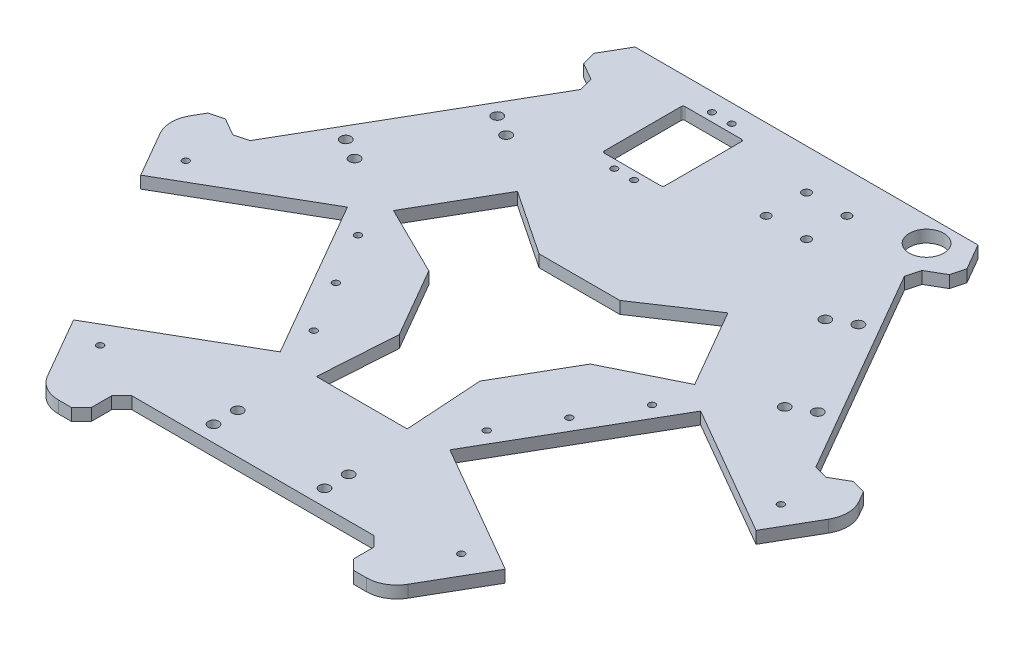
SolidWorks part; units mm, degrees
material "5052-O"
ref_plane "前基準面" through (0, 0, 0) normal (0, 0, 1) x (1, 0, 0)
ref_plane "上基準面" through (0, 0, 0) normal (0, 1, 0) x (1, 0, 0)
ref_plane "右基準面" through (0, 0, 0) normal (1, 0, 0) x (0, 0, -1)
sketch "草圖1" plane through (0, 0, 0) normal (0, 1, 0) x (1, 0, 0)
  line L1 (85, 147.2243) -> (-85, 147.2243)
  line L2 (-85, 147.2243) -> (-170, 0)
  line L3 (-170, 0) -> (-85, -147.2243)
  line L4 (-85, -147.2243) -> (85, -147.2243)
  line L5 (85, -147.2243) -> (170, 0)
  line L6 (170, 0) -> (85, 147.2243)
  circle A0 centre (0, 0) radius 147.2243 construction
  dimension "D1" = 170
extrude "填料-伸長1" add sketch "草圖1" along normal blind 6
ref_axis "基準軸1" through (0, -0.25, 0) along (0, 1, 0)
sketch "草圖46" plane through (0, 6, 0) normal (0, 1, 0) x (1, 0, 0)
  line L0 (-65, -147.2243) -> (65, -147.2243)
  line L1 (-65, -147.2243) -> (-65, -127.2243)
  line L2 (65, -147.2243) -> (65, -127.2243)
  line L3 (-65, -127.2243) -> (65, -127.2243)
  line L4 (-85, -147.2243) -> (85, -147.2243) construction
  point P6 (0, -147.2243)
  point P7 (0, -147.2243)
  dimension "D1" = 20
  dimension "D2" = 130
extrude "除料-伸長31" cut sketch "草圖46" against normal up to next
sketch "草圖8" plane through (0, 6, 0) normal (0, 1, 0) x (1, 0, 0)
  line L0 (65, -127.2243) -> (-65, -127.2243) construction
  line L2 (-27.5, -107.2243) -> (27.5, -107.2243) construction
  line L3 (-27.5, -107.2243) -> (-27.5, -119.2243) construction
  line L4 (-27.5, -119.2243) -> (27.5, -119.2243) construction
  line L5 (27.5, -107.2243) -> (27.5, -119.2243) construction
  circle A0 centre (-27.5, -119.2243) radius 2.6
  circle A1 centre (27.5, -119.2243) radius 2.6
  circle A2 centre (-27.5, -107.2243) radius 2.6
  circle A3 centre (27.5, -107.2243) radius 2.6
  point P7 (0, -119.2243)
  point P14 (0, -127.2243)
  dimension "D3" = 5.2
  dimension "D1" = 55
  dimension "D2" = 12
  dimension "D4" = 8
extrude "除料-伸長6" cut sketch "草圖8" against normal through all
pattern_circular "環狀複製排列1" count 3 over 360 about axis through (0, -0.25, 0) along (0, 1, 0) of "除料-伸長6", "除料-伸長31"
chamfer "導角1" distance 5 angle 45 12 edges at (65, 3, 127.2243) (65, 3, 147.2243) (-65, 3, 147.2243) (-65, 3, 127.2243) (77.6795, 3, -119.9038) (95, 3, -129.9038) (160, 3, -17.3205) (142.6795, 3, -7.3205) (-160, 3, -17.3205) (-142.6795, 3, -7.3205) (-77.6795, 3, -119.9038) (-95, 3, -129.9038)
sketch "草圖5" plane through (0, 6, 0) normal (0, 1, 0) x (1, 0, 0)
  line L0 (-152.5, -30.3109) -> (-107, -109.1192)
  line L1 (-152.5, -30.3109) -> (-87.5481, 7.1891)
  line L2 (-107, -109.1192) -> (-42.0481, -71.6192)
  line L3 (-87.5481, 7.1891) -> (-42.0481, -71.6192)
  line L4 (-170, 0) -> (-85, -147.2243) construction
  dimension "D1" = 75
  dimension "D2" = 91
  dimension "35" = 35
extrude "除料-伸長4" cut sketch "草圖5" against normal through all
sketch "草圖9" plane through (0, 6, 0) normal (0, 1, 0) x (1, 0, 0)
  line L0 (-64.7981, -32.215) -> (-118.4917, -63.215) construction
  line L1 (-42.0481, -71.6192) -> (-87.5481, 7.1891) construction
  line L2 (-118.4917, -63.215) -> (-89.4917, -113.4445) construction
  line L3 (-118.4917, -63.215) -> (-147.4917, -12.9856) construction
  circle A0 centre (-89.4917, -113.4445) radius 1.65
  circle A1 centre (-147.4917, -12.9856) radius 1.65
  dimension "D2" = 3.3
  dimension "D1" = 58
  dimension "D3" = 62
  dimension "D4" = 58
extrude "除料-伸長7" cut sketch "草圖9" against normal through all
mirror "鏡射1" about plane through (0, 0, 0) normal (1, 0, 0) of "除料-伸長4", "除料-伸長7"
fillet "圓角1" radius 15 4 edges at (170, 3, 0) (85, 3, 147.2243) (-170, 3, 0) (-85, 3, 147.2243)
sketch "草圖36" plane through (0, 6, 0) normal (0, 1, 0) x (1, 0, 0)
  line L0 (-72.8699, -2.2343) -> (-57.8699, -28.215) construction
  line L1 (-42.0481, -71.6192) -> (-87.5481, 7.1891) construction
  line L2 (-42.8699, -54.1958) -> (-57.8699, -28.215) construction
  line L3 (-57.8699, -28.215) -> (-64.7981, -32.215) construction
  circle A0 centre (-57.8699, -28.215) radius 1.25
  circle A1 centre (-42.8699, -54.1958) radius 1.25
  circle A2 centre (-72.8699, -2.2343) radius 1.25
  point P7 (-50.3699, -41.2054)
  point P10 (-64.7981, -32.215)
  dimension "D3" = 2.5
  dimension "D1" = 30
  dimension "D2" = 30
  dimension "D4" = 8
hole_wizard "M4x0.7 螺紋孔4" positions "草圖40" profile "草圖41" tap size "M4x0.7" standard "Ansi Metric" end condition through all
sketch "草圖40" plane through (0, 6, 0) normal (0, 1, 0) x (1, 0, 0)
  point P0 (-72.8699, -2.2343)
  point P3 (-57.8699, -28.215)
  point P6 (-42.8699, -54.1958)
sketch "草圖41" plane through (-72.8699, 6, 2.2343) normal (1, 0, 0) x (0, 0, 1)
  line L0 (0, 0) -> (0, 6)
  line L1 (0, 6) -> (1.65, 6)
  line L2 (1.65, 6) -> (1.65, 0)
  line L5 (1.65, 0) -> (0, 0)
  line L11 (0, -6.35) -> (0, 107.95) construction
  dimension "貫穿螺孔鑽直徑" = 3.3
  dimension "貫穿螺孔鑽深度" = 6
cosmetic thread "鑽孔螺紋1" parameters "D1"=10, "D2"=4.3
cosmetic thread "鑽孔螺紋2" parameters "D1"=10, "D2"=4.3
cosmetic thread "鑽孔螺紋3" parameters "D1"=10, "D2"=4.3
mirror "鏡射2" about plane through (0, 0, 0) normal (1, 0, 0) of "M4x0.7 螺紋孔4"
sketch "草圖51" plane through (0, 6, 0) normal (0, 1, 0) x (1, 0, 0)
  line L0 (85, 147.2243) -> (-85, 147.2243) construction
  line L1 (20, 34.641) -> (-20, 34.641)
  line L2 (-20, 34.641) -> (-40, 0)
  line L3 (-40, 0) -> (-20, -34.641)
  line L4 (-20, -34.641) -> (20, -34.641)
  line L5 (20, -34.641) -> (40, 0)
  line L6 (40, 0) -> (20, 34.641)
  circle A0 centre (0, 0) radius 34.641 construction
  dimension "D1" = 40
extrude "除料-伸長35" cut sketch "草圖51" against normal up to next
sketch "草圖52" plane through (0, 6, 0) normal (0, 1, 0) x (1, 0, 0)
  line L0 (-22.5, -73.2243) -> (22.5, -73.2243)
  line L5 (22.5, -73.2243) -> (20, -34.641)
  line L6 (20, -34.641) -> (-20, -34.641)
  line L7 (-20, -34.641) -> (-22.5, -73.2243)
  line L8 (60, -127.2243) -> (-60, -127.2243) construction
  line L9 (-20, 34.641) -> (-52.1641, 56.0977)
  line L10 (-52.1641, 56.0977) -> (-74.6641, 17.1266)
  line L11 (-74.6641, 17.1266) -> (-40, 0)
  line L12 (-40, 0) -> (-20, 34.641)
  line L13 (40, 0) -> (74.6641, 17.1266)
  line L14 (74.6641, 17.1266) -> (52.1641, 56.0977)
  line L15 (52.1641, 56.0977) -> (20, 34.641)
  line L16 (20, 34.641) -> (40, 0)
  line L17 (0, 0) -> (-20, -34.641) construction
  line L18 (0, 0) -> (-20, 34.641) construction
  point P8 (0, -73.2243)
  point P9 (0, -127.2243)
  dimension "D1" = 54
  dimension "D2" = 45
  dimension "D4" = 120
  dimension "D3" = 3
extrude "除料-伸長36" cut sketch "草圖52" against normal up to next
sketch "草圖53" plane through (0, 6, 0) normal (0, 1, 0) x (1, 0, 0)
  line L0 (85, 147.2243) -> (-85, 147.2243) construction
  line L1 (20, 127.2243) -> (40, 127.2243) construction
  line L2 (20, 127.2243) -> (20, 107.2243) construction
  line L3 (20, 107.2243) -> (40, 107.2243) construction
  line L4 (40, 127.2243) -> (40, 107.2243) construction
  line L5 (20, 127.2243) -> (-85, 127.2243) construction
  line L6 (-85, 127.2243) -> (-85, 147.2243) construction
  circle A0 centre (20, 127.2243) radius 2.1
  dimension "D4" = 4.2
  dimension "D1" = 20
  dimension "D2" = 20
  dimension "D3" = 20
  dimension "D5" = 90
  dimension "D6" = 105
extrude "除料-伸長37" cut sketch "草圖53" against normal up to next
pattern_linear "直線複製排列1" count 2 spacing 20 along (1, 0, 0) count 2 spacing 20 along (0, 0, 1) of "除料-伸長37"
sketch "草圖54" plane through (0, 6, 0) normal (0, 1, 0) x (1, 0, 0)
  circle A0 centre (71.5, 135.2243) radius 8.55
  circle A1 centre (40, 127.2243) radius 2.1 construction
  dimension "D1" = 17.1
  dimension "D2" = 31.5
  dimension "D3" = 8
extrude "除料-伸長38" cut sketch "草圖54" against normal up to next
sketch "草圖56" plane through (0, 0, 0) normal (0, -1, 0) x (-1, 0, 0)
  line L0 (-85, 147.2243) -> (85, 147.2243) construction
  line L2 (28.1, 89.8243) -> (28.1, 138.2243) construction
  line L3 (28.1, 138.2243) -> (37.9, 138.2243) construction
  line L4 (37.9, 138.2243) -> (37.9, 89.8243) construction
  circle A0 centre (28.1, 138.2243) radius 1.6
  circle A1 centre (37.9, 138.2243) radius 1.6
  circle A2 centre (37.9, 89.8243) radius 1.6
  circle A3 centre (28.1, 89.8243) radius 1.6
  point P2 (0, 147.2243)
  point P5 (33, 138.2243)
  dimension "D1" = 3.2
  dimension "D2" = 9
  dimension "D3" = 33
  dimension "D6" = 48.4
  dimension "D7" = 9.8
  dimension "D4" = 2
  dimension "D5" = 2
extrude "除料-伸長40" cut sketch "草圖56" against normal blind 10 contours A3 | A2 | A1 | A0
sketch "草圖55" plane through (0, 6, 0) normal (0, 1, 0) x (1, 0, 0)
  line L1 (-18, 134.0243) -> (-48, 134.0243)
  line L2 (-18, 134.0243) -> (-18, 94.0243)
  line L3 (-18, 94.0243) -> (-48, 94.0243)
  line L4 (-48, 134.0243) -> (-48, 94.0243)
  line L5 (85, 147.2243) -> (-85, 147.2243) construction
  circle A2 centre (-28.1, 138.2243) radius 1.6 construction
  point P6 (-33, 134.0243)
  point P9 (0, 147.2243)
  dimension "D3" = 4.2
  dimension "D1" = 40
  dimension "D2" = 30
  dimension "D4" = 33
extrude "除料-伸長39" cut sketch "草圖55" against normal blind 10 contours L2 L1 L4 L3
fillet "圓角2" radius 1 4 edges at (-48, 3, -94.0243) (-18, 3, -94.0243) (-18, 3, -134.0243) (-48, 3, -134.0243)
